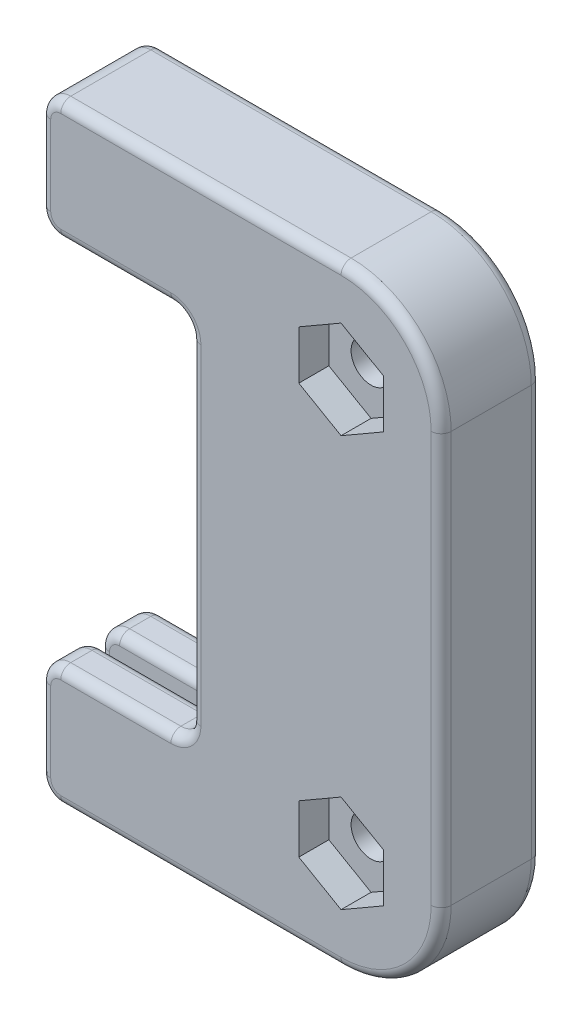
SolidWorks part; units mm, degrees
ref_plane "Front Plane" through (0, 0, 0) normal (0, 0, 1) x (1, 0, 0)
ref_plane "Top Plane" through (0, 0, 0) normal (0, 1, 0) x (1, 0, 0)
ref_plane "Right Plane" through (0, 0, 0) normal (1, 0, 0) x (0, 0, -1)
sketch "Sketch1" plane through (0, 0, 0) normal (0, 0, 1) x (1, 0, 0)
  line L0 (0, 0) -> (40, 0)
  line L1 (40, 0) -> (40, 61)
  line L2 (40, 61) -> (0, 61)
  line L3 (0, 61) -> (0, 49)
  line L4 (0, 49) -> (15, 49)
  line L5 (15, 49) -> (15, 12)
  line L6 (15, 12) -> (0, 12)
  line L7 (0, 12) -> (0, 0)
  line L8 (0, 30.5) -> (15, 30.5) construction
  line L9 (0, 5) -> (20, 5) construction
  line L10 (0, 5) -> (0, 56) construction
  line L11 (0, 56) -> (20, 56) construction
  line L12 (20, 5) -> (20, 56) construction
  dimension "D1" = 7
  dimension "D2" = 51
  dimension "D3" = 5
  dimension "D4" = 20
  dimension "D5" = 20
  dimension "D6" = 5
extrude "Boss-Extrude1" add sketch "Sketch1" along normal blind 10
sketch "Sketch2" plane through (0, 0, 0) normal (-1, 0, 0) x (0, 0, 1)
  line L0 (5, 4.925) -> (5, 0) construction
  line L1 (4.125, 4.925) -> (5.875, 4.925)
  line L2 (4.125, 4.925) -> (4.125, 56.075)
  line L3 (4.125, 56.075) -> (5.875, 56.075)
  line L4 (5.875, 4.925) -> (5.875, 56.075)
  line L5 (10, 0) -> (0, 0) construction
  line L6 (4.125, 30.5) -> (0, 30.5) construction
  line L7 (0, 49) -> (0, 12) construction
  dimension "D1" = 51.15
  dimension "D2" = 1.75
extrude "Cut-Extrude1" cut sketch "Sketch2" against normal blind 20
sketch "Sketch3" plane through (0, 0, 10) normal (0, 0, 1) x (1, 0, 0)
  line L0 (30, 51) -> (30, 10) construction
  line L1 (0, 0) -> (40, 0) construction
  line L2 (40, 0) -> (40, 61) construction
  line L3 (40, 61) -> (0, 61) construction
  circle A0 centre (30, 10) radius 2
  circle A1 centre (30, 51) radius 2
  dimension "D4" = 4
  dimension "D1" = 10
  dimension "D2" = 10
  dimension "D3" = 10
extrude "Cut-Extrude2" cut sketch "Sketch3" against normal up to surface (10 mm away) up to face at (13.75, 30.5, 0)
fillet "Fillet1" radius 10 2 edges at (40, 61, 5) (40, 0, 5)
fillet "Fillet2" radius 2 10 edges at (0, 61, 5) (0, 49, 7.9375) (0, 49, 2.0625) (15, 49, 2.0625) (15, 49, 7.9375) (15, 12, 2.0625) (15, 12, 7.9375) (0, 12, 2.0625) (0, 12, 7.9375) (0, 0, 5)
fillet "Fillet3" radius 1 52 edges at (0, 53.5375, 5.875) (0.5858, 49.5858, 5.875) (7.5, 49, 5.875) (14.4142, 48.4142, 5.875) (15, 30.5, 5.875) (14.4142, 12.5858, 5.875) (7.5, 12, 5.875) (0.5858, 11.4142, 5.875) (0.5858, 11.4142, 10) (7.5, 12, 10) (14.4142, 12.5858, 10) (15, 30.5, 10) (14.4142, 48.4142, 10) (7.5, 49, 10) (0.5858, 49.5858, 10) (0, 55, 10) (0.5858, 60.4142, 10) (16, 61, 10) (37.0711, 58.0711, 10) (40, 30.5, 10) (37.0711, 2.9289, 10) (16, 0, 10) (0.5858, 0.5858, 10) (0.5858, 11.4142, 0) (7.5, 12, 0) (14.4142, 12.5858, 0) (15, 30.5, 0) (14.4142, 48.4142, 0) (7.5, 49, 0) (0.5858, 49.5858, 0) (0, 55, 0) (0.5858, 60.4142, 0) (16, 61, 0) (37.0711, 58.0711, 0) (40, 30.5, 0) (37.0711, 2.9289, 0) (16, 0, 0) (0.5858, 0.5858, 0) (0, 53.5375, 4.125) (0.5858, 49.5858, 4.125) (7.5, 49, 4.125) (14.4142, 48.4142, 4.125) (15, 30.5, 4.125) (14.4142, 12.5858, 4.125) (7.5, 12, 4.125) (0.5858, 11.4142, 4.125) (0, 4.925, 5) (0, 7.4625, 5.875) (0, 6, 10) (0, 6, 0) (0, 7.4625, 4.125) (0, 56.075, 5)
sketch "Sketch4" plane through (0, 0, 10) normal (0, 0, 1) x (1, 0, 0)
  line L1 (30, 46.1286) -> (34.2188, 48.5643)
  line L2 (34.2188, 48.5643) -> (34.2187, 53.4357)
  line L3 (34.2187, 53.4357) -> (30, 55.8714)
  line L4 (30, 55.8714) -> (25.7812, 53.4357)
  line L5 (25.7812, 53.4357) -> (25.7812, 48.5643)
  line L6 (25.7812, 48.5643) -> (30, 46.1286)
  line L7 (30, 5.1286) -> (34.2188, 7.5643)
  line L8 (34.2188, 7.5643) -> (34.2188, 12.4357)
  line L9 (34.2188, 12.4357) -> (30, 14.8714)
  line L10 (30, 14.8714) -> (25.7812, 12.4357)
  line L11 (25.7812, 12.4357) -> (25.7812, 7.5643)
  line L12 (25.7812, 7.5643) -> (30, 5.1286)
  circle A0 centre (30, 51) radius 4.2187 construction
  circle A1 centre (30, 10) radius 4.2188 construction
  dimension "D1" = 8.4375
extrude "Cut-Extrude3" cut sketch "Sketch4" against normal blind 3
